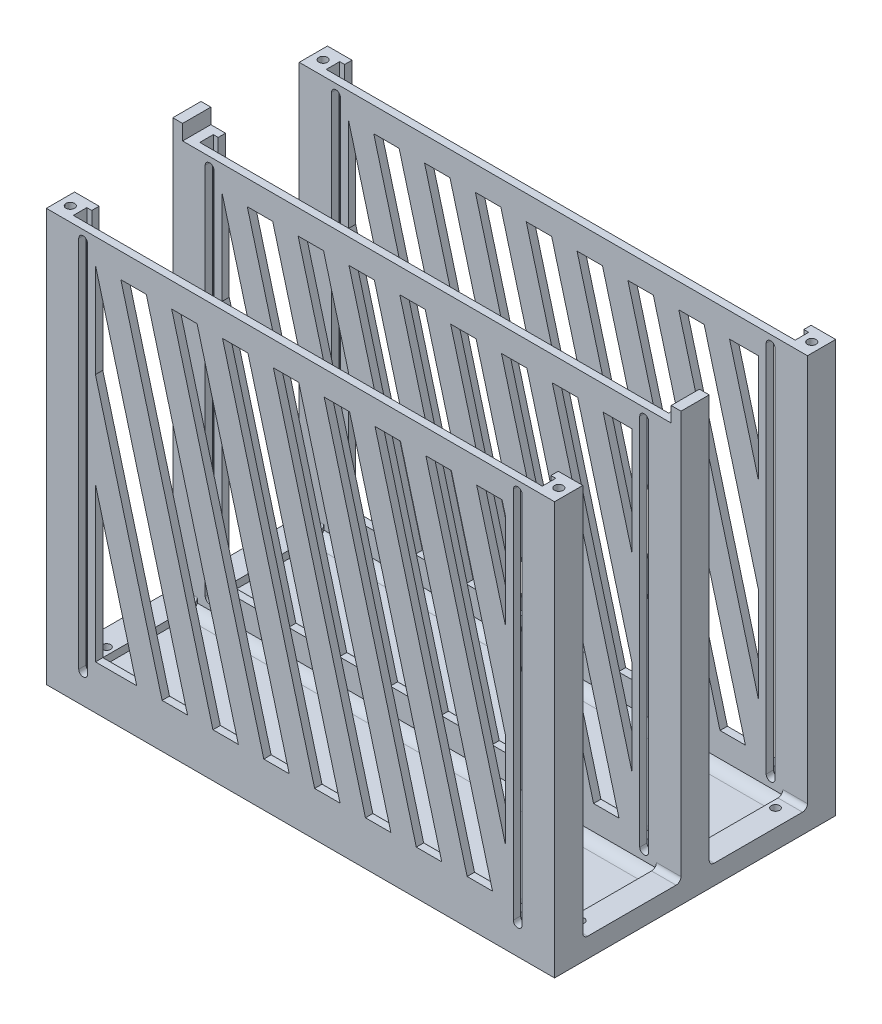
SolidWorks part; units mm, degrees
ref_plane "Front Plane" through (0, 0, 0) normal (0, 0, 1) x (1, 0, 0)
ref_plane "Top Plane" through (0, 0, 0) normal (0, 1, 0) x (1, 0, 0)
ref_plane "Right Plane" through (0, 0, 0) normal (1, 0, 0) x (0, 0, -1)
sketch "Sketch1" plane through (0, 0, 0) normal (0, 1, 0) x (1, 0, 0)
  line L0 (-95.5, 0) -> (95.5, 0) construction
  line L5 (-95.5, 2.75) -> (-93.5, 2.75)
  line L6 (-95.5, -2.75) -> (-95.5, 2.75)
  line L7 (-93.5, 2.75) -> (-93.5, 5.75)
  line L8 (-93.5, 5.75) -> (-103.5, 5.75)
  line L9 (-103.5, 5.75) -> (-103.5, -5.75)
  line L10 (-103.5, -5.75) -> (-93.5, -5.75)
  line L11 (-93.5, -5.75) -> (-93.5, -2.75)
  line L12 (-93.5, -2.75) -> (-95.5, -2.75)
  line L13 (-93.5, -2.75) -> (-93.5, -36.1204) construction
  line L14 (0, -55) -> (0, 55) construction
  line L15 (93.5, -5.75) -> (93.5, -2.75)
  line L16 (103.5, -5.75) -> (93.5, -5.75)
  line L17 (103.5, 5.75) -> (103.5, -5.75)
  line L18 (93.5, 5.75) -> (103.5, 5.75)
  line L19 (93.5, 2.75) -> (93.5, 5.75)
  line L20 (95.5, 2.75) -> (93.5, 2.75)
  line L21 (95.5, -2.75) -> (95.5, 2.75)
  line L22 (93.5, -2.75) -> (95.5, -2.75)
  line L23 (-93.5, 5.75) -> (93.5, 5.75)
  line L24 (-93.5, -5.75) -> (93.5, -5.75)
  line L25 (-93.5, -2.75) -> (93.5, -2.75)
  line L26 (93.5, 2.75) -> (-93.5, 2.75)
  line L27 (-93.5, -54.25) -> (-95.5, -54.25)
  line L28 (-95.5, -54.25) -> (-95.5, -48.75)
  line L29 (-95.5, -48.75) -> (-93.5, -48.75)
  line L30 (-93.5, -48.75) -> (-93.5, -45.75)
  line L31 (-93.5, -45.75) -> (-103.5, -45.75)
  line L32 (-103.5, -45.75) -> (-103.5, -57.25)
  line L33 (-103.5, -57.25) -> (-93.5, -57.25)
  line L34 (-93.5, -57.25) -> (-93.5, -54.25)
  line L35 (93.5, -57.25) -> (93.5, -54.25)
  line L36 (93.5, -54.25) -> (95.5, -54.25)
  line L37 (95.5, -54.25) -> (95.5, -48.75)
  line L38 (95.5, -48.75) -> (93.5, -48.75)
  line L39 (93.5, -48.75) -> (93.5, -45.75)
  line L40 (93.5, -45.75) -> (103.5, -45.75)
  line L41 (103.5, -45.75) -> (103.5, -57.25)
  line L42 (103.5, -57.25) -> (93.5, -57.25)
  line L43 (-93.5, -45.75) -> (93.5, -45.75)
  line L44 (93.5, -48.75) -> (-93.5, -48.75)
  line L45 (-93.5, -54.25) -> (93.5, -54.25)
  line L46 (-93.5, -57.25) -> (93.5, -57.25)
  line L47 (-93.5, -105.75) -> (-95.5, -105.75)
  line L48 (-95.5, -105.75) -> (-95.5, -100.25)
  line L49 (-95.5, -100.25) -> (-93.5, -100.25)
  line L50 (-93.5, -100.25) -> (-93.5, -97.25)
  line L51 (-93.5, -97.25) -> (-103.5, -97.25)
  line L52 (-103.5, -97.25) -> (-103.5, -108.75)
  line L53 (-103.5, -108.75) -> (-93.5, -108.75)
  line L54 (-93.5, -108.75) -> (-93.5, -105.75)
  line L55 (93.5, -108.75) -> (93.5, -105.75)
  line L56 (93.5, -105.75) -> (95.5, -105.75)
  line L57 (95.5, -105.75) -> (95.5, -100.25)
  line L58 (95.5, -100.25) -> (93.5, -100.25)
  line L59 (93.5, -100.25) -> (93.5, -97.25)
  line L60 (93.5, -97.25) -> (103.5, -97.25)
  line L61 (103.5, -97.25) -> (103.5, -108.75)
  line L62 (103.5, -108.75) -> (93.5, -108.75)
  line L63 (-93.5, -97.25) -> (93.5, -97.25)
  line L64 (93.5, -100.25) -> (-93.5, -100.25)
  line L65 (-93.5, -105.75) -> (93.5, -105.75)
  line L66 (-93.5, -108.75) -> (93.5, -108.75)
  line L67 (-103.5, -5.75) -> (-103.5, -45.75)
  line L68 (-93.5, -5.75) -> (-93.5, -45.75)
  line L69 (93.5, -5.75) -> (93.5, -45.75)
  line L70 (103.5, -5.75) -> (103.5, -45.75)
  line L71 (103.5, -57.25) -> (103.5, -97.25)
  line L72 (93.5, -97.25) -> (93.5, -57.25)
  line L73 (-103.5, -97.25) -> (-103.5, -57.25)
  line L74 (-93.5, -97.25) -> (-93.5, -57.25)
  line L75 (0, 5.75) -> (0, 9.75) construction
  line L76 (-96.5, 9.75) -> (96.5, 9.75) construction
  line L77 (-100.5, 9.75) -> (-103.5, 5.75)
  line L78 (-96.5, 8.05) -> (-96.5, 5.75) construction
  line L79 (-92.5, 9.75) -> (-89.5, 5.75)
  line L80 (92.5, 9.75) -> (89.5, 5.75)
  line L81 (100.5, 9.75) -> (103.5, 5.75)
  line L82 (-103.5, -51.5) -> (103.5, -51.5) construction
  line L83 (100.5, -112.75) -> (103.5, -108.75)
  line L84 (92.5, -112.75) -> (89.5, -108.75)
  line L85 (-92.5, -112.75) -> (-89.5, -108.75)
  line L86 (-100.5, -112.75) -> (-103.5, -108.75)
  circle A1 centre (96.5, 9.75) radius 1.7
  circle A2 centre (-96.5, 9.75) radius 1.7
  circle A4 centre (-96.5, 9.75) radius 4
  circle A5 centre (96.5, 9.75) radius 4
  circle A7 centre (96.5, 9.75) radius 1.7
  circle A8 centre (96.5, -112.75) radius 1.7
  circle A9 centre (96.5, -112.75) radius 4
  circle A10 centre (-96.5, -112.75) radius 1.7
  circle A12 centre (-96.5, -112.75) radius 4
  point P3 (0, 0)
  point P6 (95.5, 0)
  point P9 (-95.5, 0)
  point P61 (0, 9.75)
  dimension "D11" = 3.4
  dimension "D12" = 4
  dimension "D1" = 191
  dimension "D2" = 5.5
  dimension "D3" = 2
  dimension "D4" = 3
  dimension "D5" = 3
  dimension "D6" = 2
  dimension "D7" = 10
  dimension "D8" = 193
  dimension "D10" = 40
  dimension "D9" = 3
extrude "Boss-Extrude1" add sketch "Sketch1" against normal blind 3.2 contours L53 L54 L47 L48 L49 L50 L51 L52 | L54 L66 L55 L65 | L64 L59 L63 L50 | L34 L46 L35 L45 | L33 L34 L27 L28 L29 L30 L31 L32 | L44 L39 L43 L30 | L25 L11 L24 L15 | L26 L19 L23 L7 | L22 L15 L16 L17 L18 L19 L20 L21 | L42 L41 L40 L39 L38 L37 L36 L35 | L62 L61 L60 L59 L58 L57 L56 L55 | L11 L12 L6 L5 L7 L8 L9 L10 | L51 L74 L33 L73 | L68 L10 L67 L31 | L72 L60 L71 L42 | L70 L16 L69 L40 region at (-98.9231, 0, 0) region at (0, 0, -4.25) region at (98.9231, 0, 0) region at (0, 0, 4.25) region at (-98.5, 0, 25.75) region at (98.5, 0, 25.75) region at (0, 0, 47.25) region at (-98.9231, 0, 51.5) region at (98.9231, 0, 51.5) region at (-98.5, 0, 77.25) region at (0, 0, 55.75) region at (-98.9231, 0, 103) region at (98.5, 0, 77.25) region at (0, 0, 98.75) region at (98.9231, 0, 103) region at (0, 0, 107.25)
extrude "Boss-Extrude2" add sketch "Sketch1<4>" along normal blind 160 contours L53 L54 L47 L48 L49 L50 L51 L52 | L33 L34 L27 L28 L29 L30 L31 L32 | L11 L12 L6 L5 L7 L8 L9 L10 | L62 L61 L60 L59 L58 L57 L56 L55 | L42 L41 L40 L39 L38 L37 L36 L35 | L22 L15 L16 L17 L18 L19 L20 L21 region at (-98.9231, 0, 0) region at (98.9231, 0, 0) region at (-98.9231, 0, 51.5) region at (98.9231, 0, 51.5) region at (-98.9231, 0, 103) region at (98.9231, 0, 103)
sketch "Sketch1<4>" plane through (0, 0, 0) normal (0, 1, 0) x (1, 0, 0) same geometry as "Sketch1"
extrude "Boss-Extrude3" add sketch "Sketch1<5>" against normal blind 5 from offset 3 contours L53 L54 L47 L48 L49 L50 L51 L52 | L54 L66 L55 L65 | L47 L65 L56 L57 L58 L64 L49 L48 | L64 L59 L63 L50 | L51 L74 L33 L73 | L33 L34 L27 L28 L29 L30 L31 L32 | L34 L46 L35 L45 | L44 L39 L43 L30 | L68 L10 L67 L31 | L11 L12 L6 L5 L7 L8 L9 L10 | L25 L11 L24 L15 | L26 L19 L23 L7 | L22 L15 L16 L17 L18 L19 L20 L21 | L70 L16 L69 L40 | L42 L41 L40 L39 L38 L37 L36 L35 | L72 L60 L71 L42 | L62 L61 L60 L59 L58 L57 L56 L55 | L27 L45 L36 L37 L38 L44 L29 L28 | L20 L26 L5 L6 L12 L25 L22 L21 | L74 L63 L72 L46 | L69 L24 L68 L43 region at (-98.9231, 0, 0) region at (0, 0, 0) region at (0, 0, -4.25) region at (98.9231, 0, 0) region at (0, 0, 4.25) region at (-98.5, 0, 25.75) region at (0, 0, 25.75) region at (98.5, 0, 25.75) region at (0, 0, 47.25) region at (-98.9231, 0, 51.5) region at (98.9231, 0, 51.5) region at (0, 0, 51.5) region at (-98.5, 0, 77.25) region at (0, 0, 55.75) region at (0, 0, 77.25) region at (-98.9231, 0, 103) region at (98.5, 0, 77.25) region at (0, 0, 98.75) region at (98.9231, 0, 103) region at (0, 0, 103) region at (0, 0, 107.25) offset against normal yes
sketch "Sketch1<5>" plane through (0, 0, 0) normal (0, 1, 0) x (1, 0, 0) same geometry as "Sketch1"
fillet "Fillet1" radius 5 4 edges at (0, -3, 45.75) (0, -3, 5.75) (0, -3, 57.25) (0, -3, 97.25)
sketch "Sketch2" plane through (0, 160, 0) normal (0, 1, 0) x (1, 0, 0)
  line L0 (-95.5, 2.75) -> (-103.5, 2.75) construction
  line L1 (-103.5, 5.75) -> (-103.5, -5.75) construction
  line L2 (-95.5, -2.75) -> (-103.5, -2.75) construction
  line L3 (-99.5, 2.75) -> (-99.5, -2.75) construction
  line L4 (0, -62.975) -> (0, 62.975) construction
  line L5 (-95.5, -48.75) -> (-103.5, -48.75) construction
  line L6 (-103.5, -45.75) -> (-103.5, -57.25) construction
  line L7 (-95.5, -54.25) -> (-103.5, -54.25) construction
  line L8 (-99.5, -48.75) -> (-99.5, -54.25) construction
  line L9 (-103.5, -51.5) -> (103.5, -51.5) construction
  line L10 (103.5, -45.75) -> (103.5, -57.25) construction
  line L11 (99.5, -45.75) -> (99.5, -57.25)
  line L12 (93.5, -45.75) -> (103.5, -45.75) construction
  line L13 (103.5, -57.25) -> (93.5, -57.25) construction
  line L14 (-99.5, -45.75) -> (-99.5, -57.25)
  line L15 (-93.5, -45.75) -> (-103.5, -45.75) construction
  line L16 (-103.5, -57.25) -> (-93.5, -57.25) construction
  line L18 (-99.5, -57.25) -> (-103.5, -57.25)
  line L19 (-99.5, -57.25) -> (-99.5, -45.75)
  line L20 (-99.5, -45.75) -> (-103.5, -45.75)
  line L21 (-103.5, -57.25) -> (-103.5, -45.75)
  line L22 (99.5, -45.75) -> (103.5, -45.75)
  line L23 (99.5, -45.75) -> (99.5, -57.25)
  line L24 (99.5, -57.25) -> (103.5, -57.25)
  line L25 (103.5, -45.75) -> (103.5, -57.25)
  circle A0 centre (-99.5, 0) radius 1.75
  circle A1 centre (99.5, 0) radius 1.75
  circle A2 centre (-99.5, -51.5) radius 1.75 construction
  circle A3 centre (99.5, -51.5) radius 1.75 construction
  circle A4 centre (-99.5, -103) radius 1.75
  circle A5 centre (99.5, -103) radius 1.75
  dimension "D1" = 3.5
  dimension "D2" = 3
extrude "Cut-Extrude1" cut sketch "Sketch2" against normal blind 5 contours A0 | A1 | A5 | A4 region at (-99.5, 160, 0) region at (99.5, 160, 0) region at (-99.5, 160, 103) region at (99.5, 160, 103)
fillet "Fillet2" radius 2 8 edges at (-98.5, 0, 5.75) (-98.5, 0, 57.25) (-98.5, 0, 45.75) (-98.5, 0, 97.25) (98.5, 0, 45.75) (98.5, 0, 5.75) (98.5, 0, 57.25) (98.5, 0, 97.25)
sketch "Sketch3" plane through (0, 0, 108.75) normal (0, 0, 1) x (1, 0, 0)
  line L0 (-93.5, 160) -> (93.5, 160)
  line L1 (-93.5, 160) -> (93.5, 0) construction
  line L2 (-93.5, 160) -> (93.5, 160)
  line L3 (-93.5, 160) -> (-93.5, 0)
  line L4 (-93.5, 0) -> (93.5, 0)
  line L5 (93.5, 160) -> (93.5, 0)
  line L6 (-83.5, 150) -> (-45.9871, 10)
  line L7 (-83.5, 10) -> (83.5, 10)
  line L8 (-83.5, 10) -> (-83.5, 150)
  line L9 (-83.5, 150) -> (83.5, 150)
  line L10 (83.5, 10) -> (83.5, 150)
  line L11 (0, 150) -> (0, 10) construction
  line L12 (-83.5, 80) -> (83.5, 80) construction
  line L13 (-73.1472, 150) -> (-35.6344, 10)
  line L14 (-52.4417, 150) -> (-14.9288, 10)
  line L15 (-62.7945, 150) -> (-25.2816, 10)
  line L16 (-31.7362, 150) -> (5.7767, 10)
  line L17 (-42.089, 150) -> (-4.5761, 10)
  line L18 (-11.0307, 150) -> (26.4822, 10)
  line L19 (-21.3834, 150) -> (16.1295, 10)
  line L20 (9.6749, 150) -> (47.1877, 10)
  line L21 (-0.6779, 150) -> (36.835, 10)
  line L22 (30.3804, 150) -> (67.8933, 10)
  line L23 (20.0276, 150) -> (57.5405, 10)
  line L24 (51.0859, 150) -> (88.5988, 10)
  line L25 (40.7331, 150) -> (78.246, 10)
  line L26 (71.7914, 150) -> (83.5, 106.303)
  line L27 (61.4387, 150) -> (83.5, 67.666)
  line L28 (-88.5, 160) -> (-88.5, 156) construction
  line L29 (82.1442, 150) -> (83.5, 144.94)
  line L30 (-56.3399, 10) -> (-83.5, 111.363)
  line L31 (-83.5, 72.7259) -> (-66.6926, 10)
  line L32 (98.412, 127.9247) -> (99.5066, 123.8397) [skipped]
  line L33 (-90.3, 156) -> (-90.3, 4)
  line L34 (-86.7, 4) -> (-86.7, 156)
  line L35 (86.7, 4) -> (86.7, 156)
  line L36 (90.3, 156) -> (90.3, 4)
  circle A1 centre (-88.5, 156) radius 1.8
  circle A2 centre (-88.5, 4) radius 1.8
  circle A3 centre (88.5, 4) radius 1.8
  circle A4 centre (88.5, 156) radius 1.8
  point P6 (0, 80)
  point P40 (-88.5, 160)
  point P53 (-88.5, 0)
  line M38 (93.5, 160) -> (93.5, 0)
  line M39 (93.5, 0) -> (-93.5, 0)
  line M40 (-93.5, 0) -> (-93.5, 160)
  dimension "D11" = 3.6
  dimension "D1" = 10
  dimension "D2" = 10
  dimension "D3" = 15
  dimension "D4" = 10
  dimension "D6" = 10
  dimension "D7" = 10
  dimension "D8" = 10
  dimension "D9" = 5
  dimension "D10" = 4
  dimension "D5" = 9
extrude "Boss-Extrude4" add sketch "Sketch3" against normal up to vertex (3 mm away) contours L0 L10 L7 L8 L9 M40 M39 M38 | L8 L31 L7 L30 | L13 L9 L6 L7 | L9 L15 L7 L14 | L9 L17 L7 L16 | L9 L19 L7 L18 | L9 L21 L7 L20 | L9 L23 L7 L22 | L9 L25 L7 L24 | L9 L27 L10 L26 | L9 L29 L10 region at (0, 157.5389, 108.75) region at (-59.5672, 80, 108.75) region at (-72.305, 51.7804, 108.75) region at (-38.8617, 80, 108.75) region at (-18.1561, 80, 108.75) region at (2.5494, 80, 108.75) region at (23.2549, 80, 108.75) region at (43.9604, 80, 108.75) region at (63.9549, 82.2044, 108.75) region at (74.793, 117.5052, 108.75) region at (83.0481, 148.3133, 108.75) up to point (-95.5, -3, 105.75)
sketch "Sketch4" plane through (0, 0, 57.25) normal (0, 0, 1) x (1, 0, 0)
  line L0 (-93.5, 160) -> (93.5, 0) construction
  line L1 (-93.5, 160) -> (93.5, 160)
  line L2 (-93.5, 160) -> (-93.5, 0)
  line L3 (-93.5, 0) -> (93.5, 0)
  line L4 (93.5, 160) -> (93.5, 0)
  line L5 (-83.5, 150) -> (-45.9871, 10)
  line L6 (-83.5, 10) -> (83.5, 10)
  line L7 (-83.5, 10) -> (-83.5, 150)
  line L8 (-83.5, 150) -> (83.5, 150)
  line L9 (83.5, 10) -> (83.5, 150)
  line L10 (0, 150) -> (0, 10) construction
  line L11 (-83.5, 80) -> (83.5, 80) construction
  line L12 (-73.1472, 150) -> (-35.6344, 10)
  line L13 (-52.4417, 150) -> (-14.9288, 10)
  line L14 (-62.7945, 150) -> (-25.2816, 10)
  line L15 (-31.7362, 150) -> (5.7767, 10)
  line L16 (-42.089, 150) -> (-4.5761, 10)
  line L17 (-11.0307, 150) -> (26.4822, 10)
  line L18 (-21.3834, 150) -> (16.1295, 10)
  line L19 (9.6749, 150) -> (47.1877, 10)
  line L20 (-0.6779, 150) -> (36.835, 10)
  line L21 (30.3804, 150) -> (67.8933, 10)
  line L22 (20.0276, 150) -> (57.5405, 10)
  line L23 (51.0859, 150) -> (88.5988, 10)
  line L24 (40.7331, 150) -> (78.246, 10)
  line L25 (71.7914, 150) -> (83.5, 106.303)
  line L26 (61.4387, 150) -> (83.5, 67.666)
  line L27 (-56.3399, 10) -> (-83.5, 111.363)
  line L28 (-66.6926, 10) -> (-83.5, 72.7259)
  line L29 (99.997, 122.0096) -> (101, 118.2662) [skipped]
  line L30 (89.6442, 122.0096) -> (91, 116.9497) [skipped]
  point P5 (0, 80)
  line M15 (93.5, 160) -> (93.5, 2)
  dimension "D1" = 10
  dimension "D2" = 10
  dimension "D3" = 15
  dimension "D4" = 10
  dimension "D6" = 10
  dimension "D7" = 10
  dimension "D8" = 10
  dimension "D5" = 9
extrude "Boss-Extrude5" add sketch "Sketch4" against normal blind 3 contours L4 L1 L2 L3 L9 L6 L7 L8 M15 | L12 L8 L5 L6 | L28 L6 L27 L7 | L8 L14 L6 L13 | L8 L16 L6 L15 | L8 L18 L6 L17 | L8 L20 L6 L19 | L8 L22 L6 L21 | L8 L24 L6 L23 | L8 L26 L9 L25 region at (0, 157.5389, 57.25) region at (-59.5672, 80, 57.25) region at (-72.305, 51.7804, 57.25) region at (-38.8617, 80, 57.25) region at (-18.1561, 80, 57.25) region at (2.5494, 80, 57.25) region at (23.2549, 80, 57.25) region at (43.9604, 80, 57.25) region at (63.9549, 82.2044, 57.25) region at (74.793, 117.5052, 57.25)
pattern_linear "LPattern1" count 2 spacing 51.5 along (0, 0, -1) of "Boss-Extrude5"
sketch "Sketch5" plane through (0, 0, 0) normal (0, 1, 0) x (1, 0, 0)
  line L0 (-103.5, -51.5) -> (103.5, -51.5) construction
  line L1 (-103.5, -45.75) -> (-103.5, -57.25) construction
  line L2 (103.5, -45.75) -> (103.5, -57.25) construction
  line L3 (0, 5.75) -> (0, -108.75) construction
  line L4 (-93.5, 5.75) -> (93.5, 5.75) construction
  line L5 (103.5, -108.75) -> (-103.5, -108.75) construction
  line L6 (103.5, -7.75) -> (93.5, -7.75) construction
  line L9 (-96.5, -11.75) -> (96.5, -11.75) construction
  circle A0 centre (96.5, -11.75) radius 1.7
  circle A1 centre (-96.5, -11.75) radius 1.7
  circle A2 centre (-96.5, -91.25) radius 1.7
  circle A3 centre (96.5, -91.25) radius 1.7
  point P21 (0, -11.75)
  dimension "D2" = 3.4
  dimension "D1" = 193
  dimension "D3" = 4
extrude "BASEPLATE HOLES" cut sketch "Sketch5" against normal blind 10 contours A1 | A0 | A3 | A2 region at (96.5, 0, 11.75) region at (-96.5, 0, 11.75) region at (-96.5, 0, 91.25) region at (96.5, 0, 91.25)
extrude "Boss-Extrude6" add sketch "Sketch2<4>" along normal blind 6.2 contours L25 L22 L11 L24 | L21 L18 L14 L20 region at (101.5, 160, 51.5) region at (-101.5, 160, 51.5)
sketch "Sketch2<4>" plane through (0, 160, 0) normal (0, 1, 0) x (1, 0, 0) same geometry as "Sketch2"
extrude "Cut-Extrude3" cut sketch "Sketch3<3>" against normal through all contours L33 A2 L34 A1 | A2 | A1 | A4 | L36 A4 L35 A3 | A3 region at (88.5, 80, 108.75) region at (88.5, 4, 108.75) region at (88.5, 156, 108.75) region at (-88.5, 80, 108.75) region at (-88.5, 156, 108.75) region at (-88.5, 4, 108.75)
sketch "Sketch3<3>" plane through (0, 0, 108.75) normal (0, 0, 1) x (1, 0, 0) same geometry as "Sketch3"
